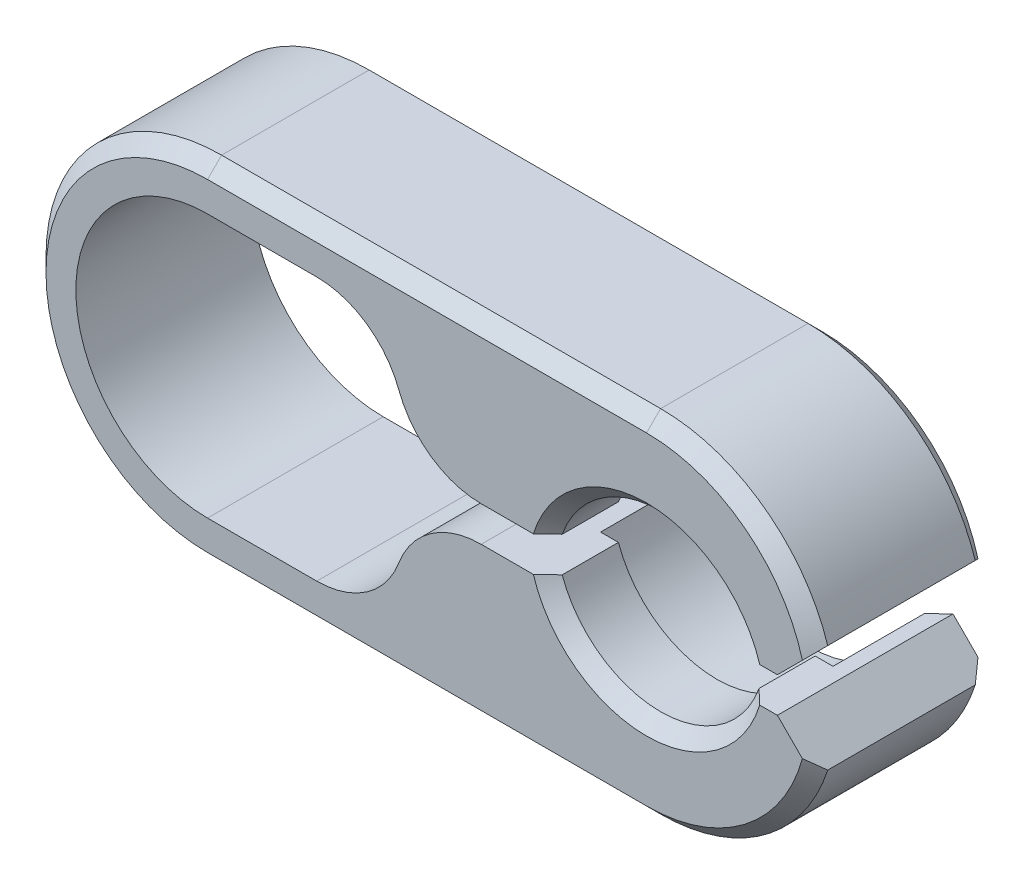
SolidWorks part; units mm, degrees
ref_plane "Front Plane" through (0, 0, 0) normal (0, 0, 1) x (1, 0, 0)
ref_plane "Top Plane" through (0, 0, 0) normal (0, 1, 0) x (1, 0, 0)
ref_plane "Right Plane" through (0, 0, 0) normal (1, 0, 0) x (0, 0, -1)
sketch "Sketch1" plane through (0, 0, 0) normal (0, 0, 1) x (1, 0, 0)
  line L0 (-12.5, 0) -> (12.5, 0) construction
  line L1 (12.5, -10) -> (-12.5, -10)
  line L2 (12.5, 10) -> (-12.5, 10)
  line L3 (0, -10) -> (0, 10) construction
  arc A0 (12.5, 10) -> (12.5, -10) centre (12.5, 0) cw
  arc A1 (-12.5, 10) -> (-12.5, -10) centre (-12.5, 0) ccw
  point P11 (12.5, 0)
  point P13 (-12.5, 0)
  dimension "D1" = 25
  dimension "D2" = 20
extrude "Boss-Extrude1" add sketch "Sketch1" along normal blind 10
ref_axis "boss axis" through (12.5, 0, 0) along (0, 0, 1)
ref_plane "Offset top" through (0, -1, 0) normal (0, 1, 0) x (1, 0, 0)
ref_plane "axis plane" through (12.5, 0, 0) normal (1, 0, 0) x (0, 0, -1)
ref_axis "cut axis" through (12.5, -1, 16.8) along (0, 0, -1)
ref_plane "cut plane" through (0, -1, 0) normal (0, 1, 0) x (0, 0, -1)
sketch "Sketch2" plane through (0, -1, 0) normal (0, 1, 0) x (0, 0, -1)
  line L0 (-10, -12.5) -> (-10, -6.55)
  line L2 (-10, -6.55) -> (-6, -6.55)
  line L3 (-6, -6.55) -> (-6, -5.585)
  line L4 (-6, -5.585) -> (0, -5.585)
  line L5 (0, 22.5) -> (0, 12.5) construction
  line L8 (-16.8, -12.5) -> (0.8, -12.5) construction
  line L9 (0, -5.585) -> (0, -12.5)
  line L10 (-10, -12.5) -> (0, -12.5)
  line L13 (-10, -12.5) -> (-10, 12.5) construction
  point P4 (0, 0)
  point P10 (0, 0)
  point P14 (0, 0)
  dimension "D1" = 6.915
  dimension "D2" = 6
  dimension "D3" = 5.95
revolve "Cut-Revolve1" cut sketch "Sketch2" angle 180 about axis through (12.5, -1, 16.8) along (0, 0, -1)
sketch "Sketch3" plane through (0, 0, 10) normal (0, 0, 1) x (1, 0, 0)
  line L0 (22.5, 1) -> (3.085, 1)
  line L1 (-12.5, 7.5) -> (-6.2825, 7.5)
  line L2 (5.5, 0) -> (-5.5, 0) construction
  line L3 (-12.5, -7.5) -> (-6.2825, -7.5)
  line L4 (22.5, -1) -> (3.085, -1)
  line L5 (22.5, 1) -> (22.5, -1)
  line L6 (3.085, 1) -> (3.085, -1) construction
  line L7 (5.585, 4.8432) -> (5.585, -5.4616) construction
  line L8 (5.5, -1) -> (-5.5, -1) construction
  arc A0 (-12.5, -7.5) -> (-12.5, 7.5) centre (-12.5, 0) cw
  arc A1 (-12.5, 10) -> (-12.5, -10) centre (-12.5, 0) ccw construction
  arc A2 (-6.2825, 7.5) -> (-1.5987, 4.25) centre (-6.2825, 2.5) cw
  arc A3 (-1.5987, 4.25) -> (3.085, 1) centre (3.085, 6) ccw
  arc A4 (-1.5987, -4.25) -> (3.085, -1) centre (3.085, -6) cw
  arc A5 (-6.2825, -7.5) -> (-1.5987, -4.25) centre (-6.2825, -2.5) ccw
  arc A6 (12.5, -10) -> (12.5, 10) centre (12.5, 0) ccw construction
  arc A8 (19.415, -1) -> (5.585, -1) centre (12.5, -1) ccw construction
  point P27 (-4.4531, 2.0622)
  dimension "D1" = 2.5
  dimension "D4" = 5
  dimension "D2" = 2.5
extrude "Cut-Extrude1" cut sketch "Sketch3" against normal through all
pattern_circular "CirPattern1" count 2 over 360 about axis through (12.5, 0, 0) along (0, 0, 1) of "Cut-Revolve1"
chamfer "Chamfer2" distance 2.5 angle 45 2 edges at (22.4499, -1, 5) (22.4499, 1, 5) first distance on face at (19.891, -1, 5.3333) first distance on face at (19.891, 1, 5.3333)
chamfer "Chamfer1" distance 0.8 angle 45 14 edges at (12.5, 4.95, 10) (12.5, 5.915, 0) (18.3873, 8.0833, 0) (18.3873, -8.0833, 0) (0, 10, 0) (0, -10, 0) (-22.5, 0, 0) (18.3873, -8.0833, 10) (0, -10, 10) (18.3873, 8.0833, 10) (-22.5, 0, 10) (0, 10, 10) (12.5, -4.95, 10) (12.5, -5.915, 0)
